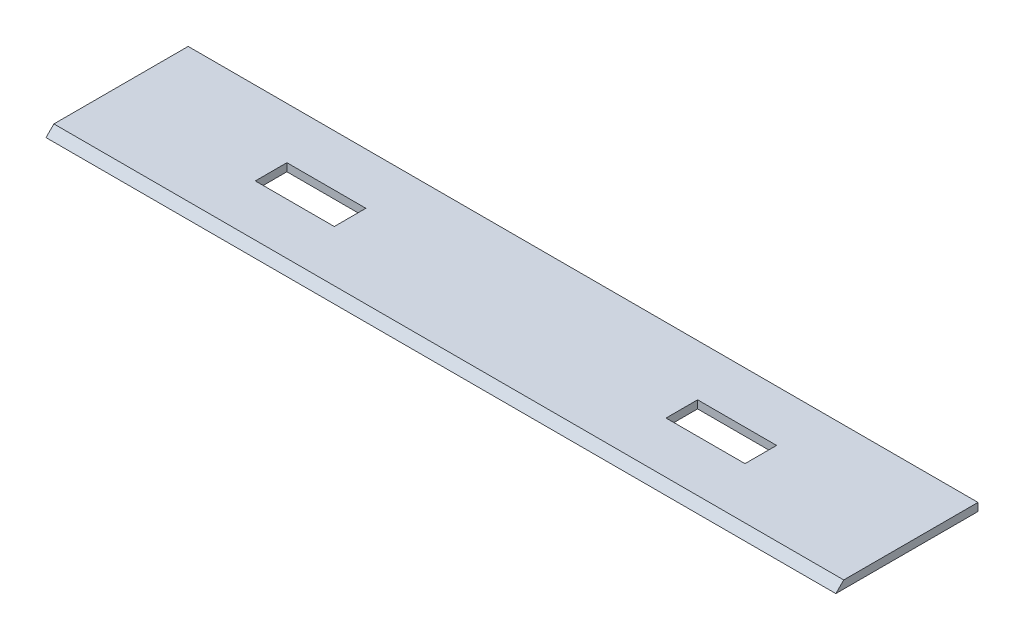
SolidWorks part; units mm, degrees
ref_plane "Спереди" through (0, 0, 0) normal (0, 0, 1) x (1, 0, 0)
ref_plane "Сверху" through (0, 0, 0) normal (0, 1, 0) x (1, 0, 0)
ref_plane "Справа" through (0, 0, 0) normal (1, 0, 0) x (0, 0, -1)
sketch "Эскиз1" plane through (0, 0, 0) normal (0, 1, 0) x (1, 0, 0)
  line L1 (-50, -9) -> (50, -9)
  line L2 (-50, -9) -> (-50, 9)
  line L3 (-50, 9) -> (50, 9)
  line L4 (50, -9) -> (50, 9)
  line L5 (-50, -9) -> (50, 9) construction
  line L6 (-50, 9) -> (50, -9) construction
  point P0 (0, 0)
  dimension "D1" = 100
  dimension "D2" = 18
extrude "Бобышка-Вытянуть1" add sketch "Эскиз1" along normal blind 1
chamfer "Фаска1" distance 1 angle 45 1 edges at (0, 1, 9)
sketch "Эскиз2" plane through (0, 1, 0) normal (0, 1, 0) x (1, 0, 0)
  line L0 (-50, 0.5) -> (50, 0.5) construction
  line L1 (-50, 9) -> (-50, -8) construction
  line L2 (50, -8) -> (50, 9) construction
  line L4 (-31, 2.5) -> (-21, 2.5)
  line L5 (-31, 2.5) -> (-31, -1.5)
  line L6 (-31, -1.5) -> (-21, -1.5)
  line L7 (-21, 2.5) -> (-21, -1.5)
  line L8 (-31, 2.5) -> (-21, -1.5) construction
  line L9 (-31, -1.5) -> (-21, 2.5) construction
  line L10 (21, 2.5) -> (31, 2.5)
  line L11 (21, 2.5) -> (21, -1.5)
  line L12 (21, -1.5) -> (31, -1.5)
  line L13 (31, 2.5) -> (31, -1.5)
  line L14 (21, 2.5) -> (31, -1.5) construction
  line L15 (21, -1.5) -> (31, 2.5) construction
  point P6 (-26, 0.5)
  point P11 (26, 0.5)
  dimension "D1" = 21
  dimension "D2" = 42
  dimension "D3" = 4
  dimension "D4" = 4
  dimension "D5" = 10
  dimension "D6" = 10
extrude "Вырез-Вытянуть1" cut sketch "Эскиз2" against normal blind 1
